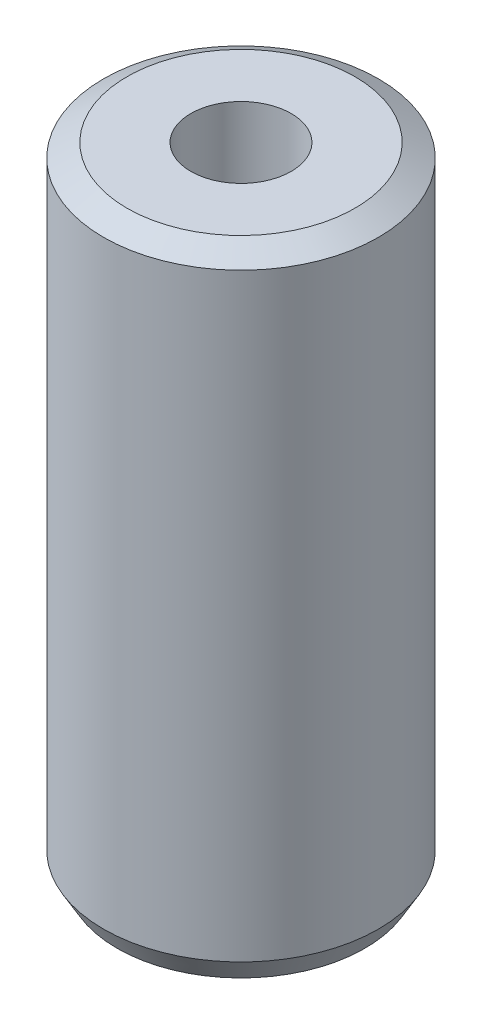
SolidWorks part; units mm, degrees
ref_plane "Front Plane" through (0, 0, 0) normal (0, 0, 1) x (1, 0, 0)
ref_plane "Top Plane" through (0, 0, 0) normal (0, 1, 0) x (1, 0, 0)
ref_plane "Right Plane" through (0, 0, 0) normal (1, 0, 0) x (0, 0, -1)
sketch "Sketch1" plane through (0, 0, 0) normal (0, 1, 0) x (1, 0, 0)
  circle A0 centre (0, 0) radius 20
  dimension "SHAFT_OD" = 40
extrude "Boss-Extrude1" add sketch "Sketch1" along normal blind 92.586
sketch "Sketch2" plane through (0, 0, 0) normal (0, 1, 0) x (1, 0, 0)
  circle A0 centre (0, 0) radius 7.3075
  dimension "BORE_D" = 14.615
extrude "Cut-Extrude1" cut sketch "Sketch2" along normal through all
chamfer "Chamfer1" distance 1.9672 angle 60 2 edges at (0, 92.586, 20) (0, 0, 20) first distance on face at (0, 92.586, 20) first distance on face at (0, 0, 7.3075)
